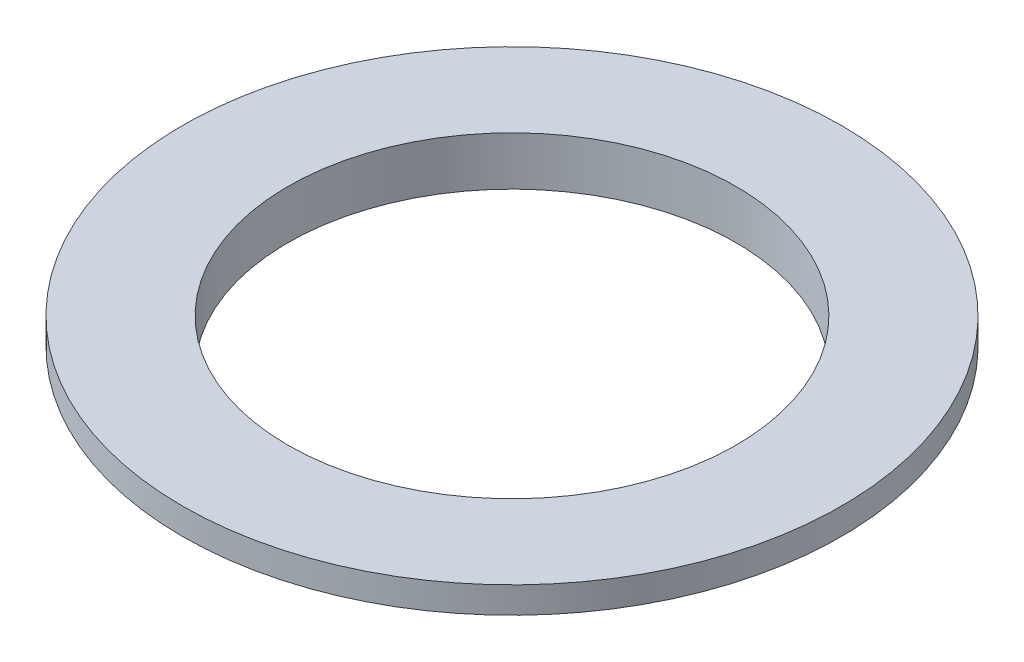
SolidWorks part; units mm, degrees
ref_plane "Front Plane" through (0, 0, 0) normal (0, 0, 1) x (1, 0, 0)
ref_plane "Top Plane" through (0, 0, 0) normal (0, 1, 0) x (1, 0, 0)
ref_plane "Right Plane" through (0, 0, 0) normal (1, 0, 0) x (0, 0, -1)
sketch "Sketch1" plane through (0, 0, 0) normal (0, 1, 0) x (1, 0, 0)
  circle A6 centre (0, 0) radius 25.4
  circle A7 centre (0, 0) radius 31.75
  circle A8 centre (0, 0) radius 21.59
  dimension "D1" = 50.8
  dimension "D2" = 6.35
  dimension "D3" = 3.81
extrude "Boss-Extrude1" add sketch "Sketch1" along normal mid plane 2.54 contours A6 A8 | A7 A6 region at (-24.6816, 0, 0) region at (-30.852, 0, 0)
extrude "Boss-Extrude2" add sketch "Sketch1<3>" against normal blind 2.159 from surface contours A6 A8 region at (-24.6816, 0, 0) starting at face at (0, -1.27, 21.59)
sketch "Sketch1<3>" plane through (0, 0, 0) normal (0, 1, 0) x (1, 0, 0) same geometry as "Sketch1"
